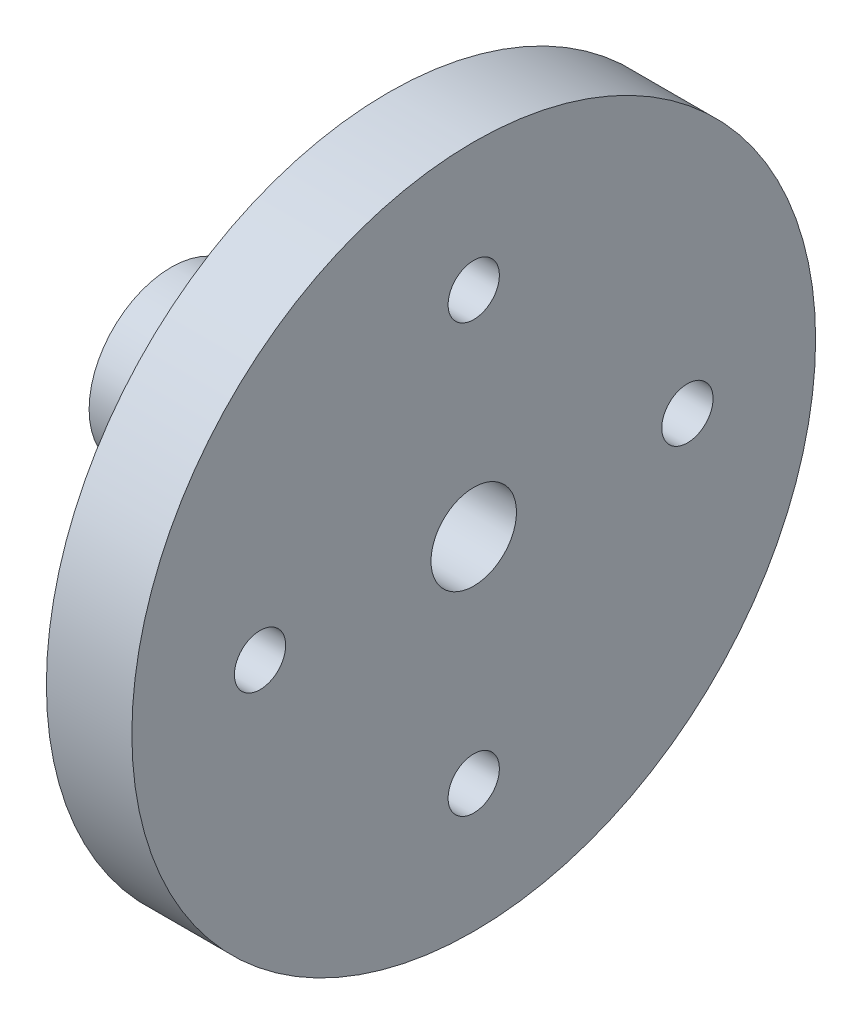
SolidWorks part; units mm, degrees
ref_plane "Front Plane" through (0, 0, 0) normal (0, 0, 1) x (1, 0, 0)
ref_plane "Top Plane" through (0, 0, 0) normal (0, 1, 0) x (1, 0, 0)
ref_plane "Right Plane" through (0, 0, 0) normal (1, 0, 0) x (0, 0, -1)
sketch "Sketch1" plane through (0, 0, 0) normal (1, 0, 0) x (0, 0, -1)
  circle A0 centre (0, 0) radius 20
  circle A1 centre (0, 0) radius 2.5
  dimension "D1" = 40
  dimension "D2" = 5
extrude "Boss-Extrude1" add sketch "Sketch1" along normal blind 5
sketch "Sketch3" plane through (0, 0, 0) normal (-1, 0, 0) x (0, 0, 1)
  circle A1 centre (0, 0) radius 4.8
  circle A2 centre (0, 0) radius 2.5
extrude "Boss-Extrude2" add sketch "Sketch3" along normal blind 12.7
hole_wizard "Ø3.0 (3) Diameter Hole1" positions "Sketch5" profile "Sketch4" hole size "Ø3.0" standard "ISO"
sketch "Sketch5" plane through (5, 0, 0) normal (1, 0, 0) x (0, 0, -1)
  point P0 (12.5, 0)
  point P2 (0, -12.5)
  point P4 (-12.5, 0)
  point P6 (0, 12.5)
  dimension "D1" = 25
  dimension "D2" = 25
  dimension "D3" = 12.5
  dimension "D4" = 12.5
sketch "Sketch4" plane through (5, 0, -12.5) normal (0, 1, 0) x (0, 0, -1)
  line L0 (0, 0) -> (0, 15.9013)
  line L1 (0, 15.9013) -> (1.5, 15)
  line L2 (1.5, 15) -> (1.5, 0)
  line L5 (1.5, 0) -> (0, 0)
  line L10 (0, 15.9013) -> (-1.5, 15) construction
  line L11 (0, -6.35) -> (0, 107.95) construction
  dimension "Hole Dia." = 3
  dimension "Hole Depth" = 15
  dimension "Drill Angle" = 118
